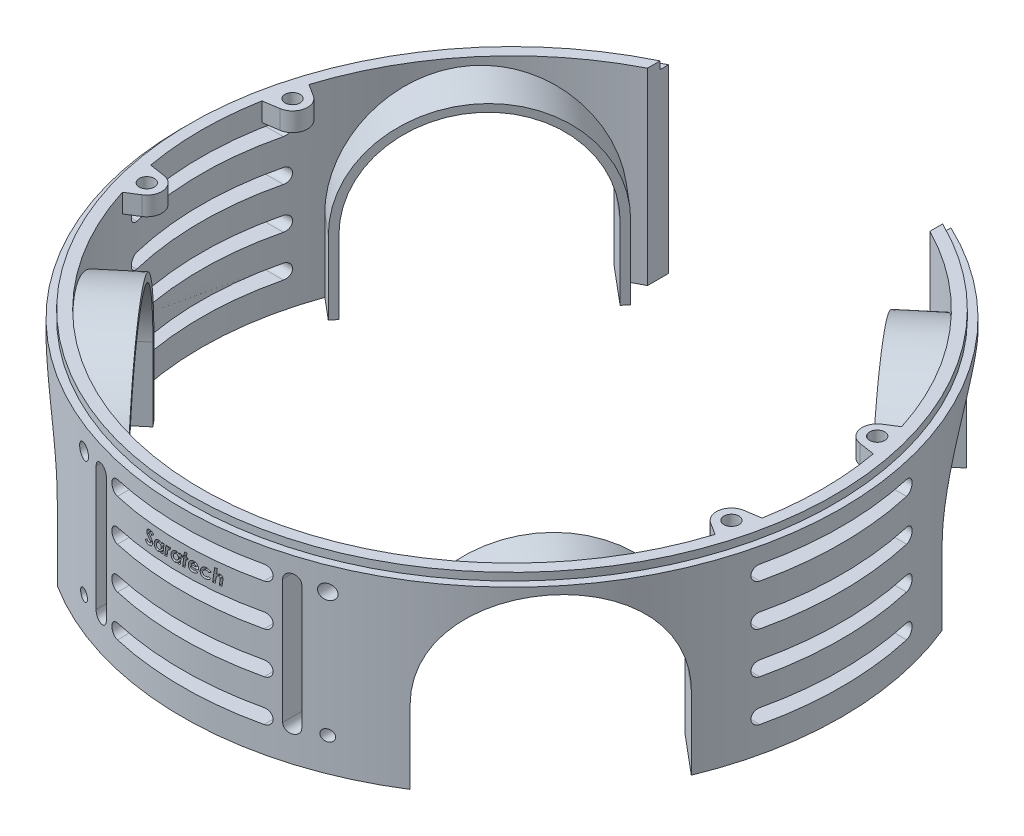
SolidWorks part; units mm, degrees
ref_plane "Front Plane" through (0, 0, 0) normal (0, 0, 1) x (1, 0, 0)
ref_plane "Top Plane" through (0, 0, 0) normal (0, 1, 0) x (1, 0, 0)
ref_plane "Right Plane" through (0, 0, 0) normal (1, 0, 0) x (0, 0, -1)
sketch "Sketch1" plane through (0, 0, 0) normal (0, 1, 0) x (1, 0, 0)
  circle A0 centre (0, 0) radius 87.5
  dimension "D1" = 175
extrude "Boss-Extrude1" add sketch "Sketch1" along normal blind 50
sketch "Sketch3" plane through (0, 50, 0) normal (0, 1, 0) x (1, 0, 0)
  line L0 (87.5, 0) -> (82.5, 0) construction
  circle A0 centre (0, 0) radius 87.5 construction
  circle A1 centre (0, 0) radius 82.5
  dimension "D1" = 5
extrude "Cut-Extrude1" cut sketch "Sketch3" against normal blind 50 contours A1 | A1 region at (0, 50, 0)
sketch "Sketch6" plane through (0, 50, 0) normal (0, 1, 0) x (1, 0, 0)
  line L0 (-37.5, 79.0569) -> (37.5, 79.0569) construction
  line L2 (-37.5, 119.3895) -> (37.5, 119.3895)
  line L3 (-37.5, 119.3895) -> (-37.5, 38.7244)
  line L4 (-37.5, 38.7244) -> (37.5, 38.7244)
  line L5 (37.5, 119.3895) -> (37.5, 38.7244)
  line L6 (-37.5, 119.3895) -> (37.5, 38.7244) construction
  line L7 (-37.5, 38.7244) -> (37.5, 119.3895) construction
  circle A1 centre (0, 0) radius 87.5 construction
  point P7 (0, 79.0569)
  circle M1 centre (0, 0) radius 82.5
  circle M2 centre (0, 0) radius 87.5
  dimension "D1" = 75
extrude "Cut-Extrude2" cut sketch "Sketch6" against normal blind 50 contours L0 M2 M1 region at (0, 50, -86.737)
sketch "Sketch7" plane through (0, 50, 0) normal (0, 1, 0) x (1, 0, 0)
  line L0 (-87.5, 0) -> (87.5, 0) construction
  line L1 (0, 0) -> (-77.6237, 19.3538) construction
  line L2 (-77.0229, 15.3991) -> (-81.1672, 14.7695)
  line L3 (-75.481, 22.7315) -> (-78.6938, 24.7695)
  line L5 (-77.6237, 21.3538) -> (-77.6237, 17.3538) construction
  circle A0 centre (-77.6237, 19.3538) radius 2
  arc A1 (-37.5, 79.0569) -> (37.5, 79.0569) centre (0, 0) ccw construction
  arc A2 (-77.0229, 15.3991) -> (-75.481, 22.7315) centre (-77.6237, 19.3538) ccw
  arc A3 (-37.5, 73.4847) -> (37.5, 73.4847) centre (0, 0) ccw construction
  arc A4 (-81.1672, 14.7695) -> (-78.6938, 24.7695) centre (0, 0) cw
  dimension "D1" = 14
  dimension "D2" = 4
  dimension "D3" = 4
  dimension "D4" = 10
  dimension "D5" = 80
extrude "Boss-Extrude10" add sketch "Sketch7" against normal blind 5
mirror "Mirror1" about plane through (0, 0, 0) normal (1, 0, 0) of "Boss-Extrude10" second plane through (0, 0, 0) second plane normal (0, 0, 1)
sketch "Sketch8" plane through (0, 0, 0) normal (0, 0, 1) x (1, 0, 0)
  line L0 (0, 0) -> (0, 50) construction
  line L1 (-87.5, 0) -> (87.5, 0) construction
  line L2 (87.5, 50) -> (-87.5, 50) construction
ref_plane "Plane2" through (0, 0, 0) normal (0.766, 0, 0.6428) x (0, 1, 0)
sketch "Sketch9" plane through (0, 0, 0) normal (0.766, 0, 0.6428) x (0, 1, 0)
  line L0 (0, 0) -> (50, 0) construction
  line L1 (19.5, 26.5) -> (0, 26.5)
  line L2 (0, 82.5) -> (0, -82.5) construction
  line L3 (0, 26.5) -> (0, -26.5)
  line L4 (0, -26.5) -> (19.5, -26.5)
  line L5 (19.5, 26.5) -> (19.5, -26.5) construction
  line L6 (0, 26.5) -> (46, 26.5) construction
  line L7 (46, 0) -> (46, 26.5) construction
  arc A0 (19.5, -26.5) -> (19.5, 26.5) centre (19.5, 0) ccw
  dimension "D1" = 53
  dimension "D2" = 46
extrude "Cut-Extrude3" cut sketch "Sketch9" against normal through all
ref_plane "Plane3" through (-53.6231, 0, -44.9951) normal (0.766, 0, 0.6428) x (0, 1, 0)
sketch "Sketch10" plane through (-53.6231, 0, -44.9951) normal (0.766, 0, 0.6428) x (0, 1, 0)
  line L0 (19.5, -26.5) -> (0, -26.5) construction
  line L1 (0, 26.5) -> (19.5, 26.5) construction
  line L2 (19.5, -26.5) -> (0, -26.5)
  line L3 (0, 26.5) -> (19.5, 26.5)
  line L4 (0, 28.5) -> (19.5, 28.5)
  line L5 (19.5, -28.5) -> (0, -28.5)
  line L6 (0, 28.5) -> (0, 26.5)
  line L7 (0, -26.5) -> (0, -28.5)
  arc A0 (19.5, -26.5) -> (19.5, 26.5) centre (19.5, 0) ccw construction
  arc A1 (19.5, -26.5) -> (19.5, 26.5) centre (19.5, 0) ccw
  arc A2 (19.5, -28.5) -> (19.5, 28.5) centre (19.5, 0) ccw
  dimension "D1" = 2
extrude "Boss-Extrude11" add sketch "Sketch10" against normal up to next
mirror "Mirror2" about plane through (0, 0, 0) normal (0, 0, 1) of "Cut-Extrude3", "Boss-Extrude11" second plane through (0, 0, 0) second plane normal (1, 0, 0)
sketch "Sketch13" plane through (0, 50, 0) normal (0, 1, 0) x (1, 0, 0)
  circle A0 centre (0, 0) radius 85.5
  circle A1 centre (0, 0) radius 87.5
  arc A2 (-37.5, 79.0569) -> (37.5, 79.0569) centre (0, 0) ccw construction
  dimension "D1" = 2
extrude "Cut-Extrude4" cut sketch "Sketch13" against normal blind 2
sketch "Sketch14" plane through (0, 0, 0) normal (1, 0, 0) x (0, 0, -1)
  line L0 (-19.464, 41.8846) -> (19.464, 41.8846) construction
  line L1 (-19.464, 43.8314) -> (19.464, 43.8314)
  line L2 (-19.464, 39.9379) -> (19.464, 39.9379)
  line L3 (0, 48) -> (0, 0) construction
  line L7 (-19.464, 28.9379) -> (19.464, 28.9379)
  line L8 (-19.464, 32.8314) -> (19.464, 32.8314)
  line L9 (-19.464, 30.8846) -> (19.464, 30.8846) construction
  line L13 (-19.464, 17.9379) -> (19.464, 17.9379)
  line L14 (-19.464, 21.8314) -> (19.464, 21.8314)
  line L15 (-19.464, 19.8846) -> (19.464, 19.8846) construction
  line L19 (-19.464, 6.9379) -> (19.464, 6.9379)
  line L20 (-19.464, 10.8314) -> (19.464, 10.8314)
  line L21 (-19.464, 8.8846) -> (19.464, 8.8846) construction
  line L25 (-19.464, 5.3314) -> (19.464, 5.3314) [skipped]
  line L26 (-19.464, 1.4379) -> (19.464, 1.4379) [skipped]
  line L27 (-19.464, 16.3314) -> (19.464, 16.3314) [skipped]
  line L28 (-19.464, 12.4379) -> (19.464, 12.4379) [skipped]
  line L29 (-19.464, 27.3314) -> (19.464, 27.3314) [skipped]
  line L30 (-19.464, 23.4379) -> (19.464, 23.4379) [skipped]
  line L31 (-19.464, 38.3314) -> (19.464, 38.3314) [skipped]
  line L32 (-19.464, 34.4379) -> (19.464, 34.4379) [skipped]
  arc A0 (-19.464, 43.8314) -> (-19.464, 39.9379) centre (-19.464, 41.8846) ccw
  arc A1 (19.464, 39.9379) -> (19.464, 43.8314) centre (19.464, 41.8846) ccw
  arc A4 (-19.464, 32.8314) -> (-19.464, 28.9379) centre (-19.464, 30.8846) ccw
  arc A5 (19.464, 28.9379) -> (19.464, 32.8314) centre (19.464, 30.8846) ccw
  arc A8 (-19.464, 21.8314) -> (-19.464, 17.9379) centre (-19.464, 19.8846) ccw
  arc A9 (19.464, 17.9379) -> (19.464, 21.8314) centre (19.464, 19.8846) ccw
  arc A12 (-19.464, 10.8314) -> (-19.464, 6.9379) centre (-19.464, 8.8846) ccw
  arc A13 (19.464, 6.9379) -> (19.464, 10.8314) centre (19.464, 8.8846) ccw
  arc A16 (-19.464, 5.3314) -> (-19.464, 1.4379) centre (-19.464, 3.3846) ccw [skipped]
  arc A17 (19.464, 1.4379) -> (19.464, 5.3314) centre (19.464, 3.3846) ccw [skipped]
  arc A18 (-19.464, 16.3314) -> (-19.464, 12.4379) centre (-19.464, 14.3846) ccw [skipped]
  arc A19 (19.464, 12.4379) -> (19.464, 16.3314) centre (19.464, 14.3846) ccw [skipped]
  arc A20 (-19.464, 27.3314) -> (-19.464, 23.4379) centre (-19.464, 25.3846) ccw [skipped]
  arc A21 (19.464, 23.4379) -> (19.464, 27.3314) centre (19.464, 25.3846) ccw [skipped]
  arc A22 (-19.464, 38.3314) -> (-19.464, 34.4379) centre (-19.464, 36.3846) ccw [skipped]
  arc A23 (19.464, 34.4379) -> (19.464, 38.3314) centre (19.464, 36.3846) ccw [skipped]
  point P2 (0, 41.8846)
  point P20 (0, 30.8846)
  point P34 (0, 19.8846)
  point P48 (0, 8.8846)
extrude "Cut-Extrude5" cut sketch "Sketch14" against normal blind 157 and the other way blind 156
pattern_circular "CirPattern1" count 2 every 90 of "Cut-Extrude5"
sketch "Sketch15" plane through (0, 0, 0) normal (0, 0, 1) x (1, 0, 0)
  line L0 (-25.3575, 41.8846) -> (-25.3575, 8.8846) construction
  line L1 (-23.4107, 41.8846) -> (-23.4107, 8.8846)
  line L2 (-27.3042, 41.8846) -> (-27.3042, 8.8846)
  line L3 (0, 43.8314) -> (0, 39.9379) construction
  line L4 (-19.464, 43.8314) -> (19.464, 43.8314) construction
  line L5 (19.464, 39.9379) -> (-19.464, 39.9379) construction
  line L6 (-27.3042, 25.3846) -> (-23.4107, 25.3846) construction
  line L7 (-32.3575, 41.8846) -> (-25.3575, 41.8846) construction
  line L8 (-32.3575, 8.8846) -> (-32.3575, 41.8846) construction
  line L9 (-15.6073, 43.8314) -> (-35.7163, 43.8314) construction
  line L18 (0, 48) -> (0, 0) construction
  line L19 (85.5, 48) -> (-85.5, 48) construction
  line L23 (25.3575, 41.8846) -> (25.3575, 8.8846) construction
  line L24 (23.4107, 41.8846) -> (23.4107, 8.8846)
  line L25 (27.3042, 41.8846) -> (27.3042, 8.8846)
  line L26 (32.3575, 8.8846) -> (30.8575, 8.8846) construction
  line L27 (32.3575, 41.8846) -> (30.4107, 41.8846) construction
  line L28 (25.3575, 41.8846) -> (32.3575, 41.8846) construction
  line L29 (32.3575, 41.8846) -> (32.3575, 41.4958) construction
  line L30 (25.3575, 8.8846) -> (32.3575, 8.8846) construction
  line L31 (32.3575, 7.2781) -> (32.3575, 8.8846) construction
  arc A0 (-23.4107, 41.8846) -> (-27.3042, 41.8846) centre (-25.3575, 41.8846) ccw
  arc A1 (-27.3042, 8.8846) -> (-23.4107, 8.8846) centre (-25.3575, 8.8846) ccw
  arc A6 (23.4107, 41.8846) -> (27.3042, 41.8846) centre (25.3575, 41.8846) cw
  arc A7 (27.3042, 8.8846) -> (23.4107, 8.8846) centre (25.3575, 8.8846) cw
  circle A8 centre (32.3575, 41.8846) radius 1.9467
  circle A10 centre (32.3575, 8.8846) radius 1.5
  circle A11 centre (-32.3575, 8.8846) radius 1.5
  circle A12 centre (-32.3575, 41.8846) radius 1.9467
  text T0 "<b><i>Saratech</i></b>\r\n"
  point P2 (-25.3575, 25.3846)
  point P52 (25.3575, 25.3846)
  dimension "D1" = 7
  dimension "D2" = 33
  dimension "D3" = 1.9467
extrude "Cut-Extrude6" cut sketch "Sketch15" along normal blind 122
sketch "Sketch16" plane through (0, 50, 0) normal (0, 1, 0) x (1, 0, 0)
  line L0 (-37.5, 76.8375) -> (37.5, 76.8375) construction
